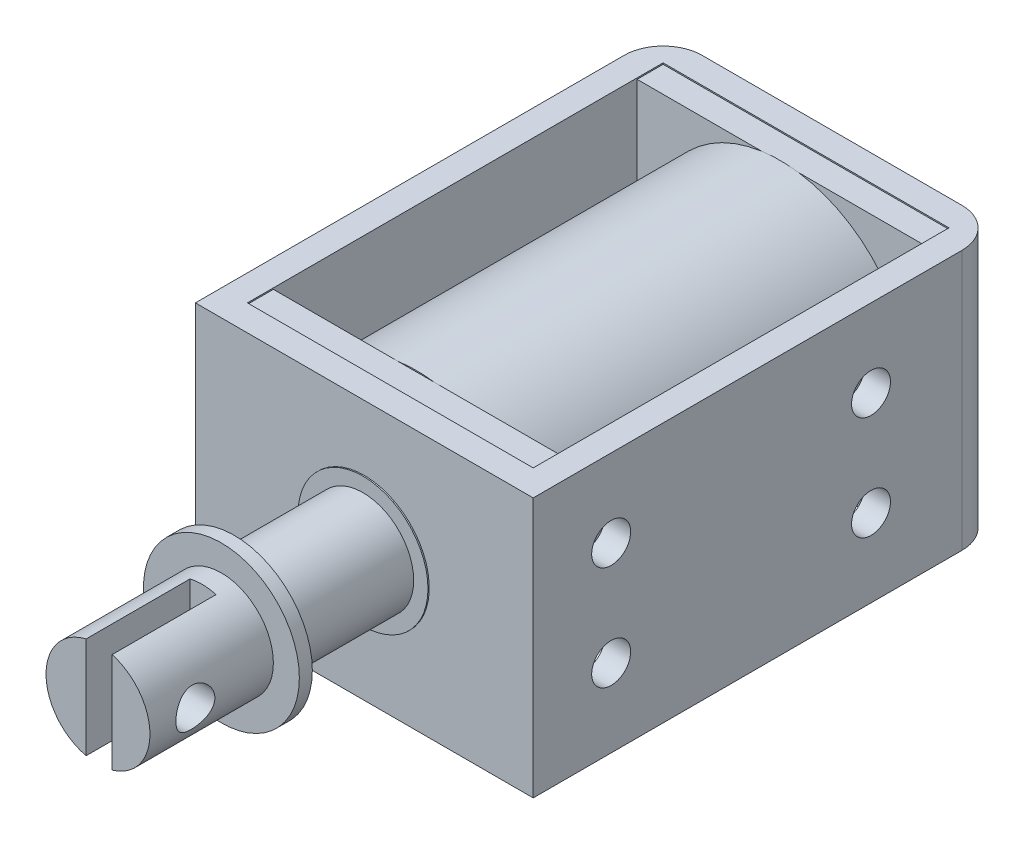
SolidWorks part; units mm, degrees
ref_plane "Front Plane" through (0, 0, 0) normal (0, 0, 1) x (1, 0, 0)
ref_plane "Top Plane" through (0, 0, 0) normal (0, 1, 0) x (1, 0, 0)
ref_plane "Right Plane" through (0, 0, 0) normal (1, 0, 0) x (0, 0, -1)
sketch "Sketch1" plane through (0, 0, 0) normal (0, 1, 0) x (1, 0, 0)
  line L1 (-13, -18) -> (13, -18)
  line L2 (-13, -18) -> (-13, 18)
  line L3 (-13, 18) -> (13, 18)
  line L4 (13, -18) -> (13, 18)
  line L5 (-13, -18) -> (13, 18) construction
  line L6 (-13, 18) -> (13, -18) construction
  point P0 (0, 0)
  dimension "D1" = 26
  dimension "D2" = 36
extrude "Boss-Extrude1" add sketch "Sketch1" along normal blind 20
fillet "Fillet1" radius 3 2 edges at (-13, 10, -18) (13, 10, -18)
sketch "Sketch2" plane through (0, 20, 0) normal (0, 1, 0) x (1, 0, 0)
  line L0 (10, 18) -> (-10, 18) construction
  line L1 (-11, -16) -> (11, -16)
  line L2 (-11, -16) -> (-11, 16)
  line L3 (-11, 16) -> (11, 16)
  line L4 (11, -16) -> (11, 16)
  line L5 (-11, -16) -> (11, 16) construction
  line L6 (-11, 16) -> (11, -16) construction
  line L7 (13, -18) -> (13, 15) construction
  point P0 (0, 0)
  dimension "D1" = 2
  dimension "D2" = 2
extrude "Cut-Extrude1" cut sketch "Sketch2" against normal up to surface (20 mm away) up to face at (0, 0, -5.2071)
sketch "Sketch5" plane through (0, 0, -16) normal (0, 0, 1) x (1, 0, 0)
  line L0 (13, 20) -> (13, 0) construction
  line L1 (-11, -0.1) -> (11, -0.1)
  line L2 (-11, -0.1) -> (-11, 19.9)
  line L3 (-11, 19.9) -> (11, 19.9)
  line L4 (11, -0.1) -> (11, 19.9)
  line L5 (-11, -0.1) -> (11, 19.9) construction
  line L6 (-11, 19.9) -> (11, -0.1) construction
  line L7 (-13, 20) -> (-13, 0) construction
  line L8 (-13, 20) -> (13, 20) construction
  line L9 (-13, 0) -> (13, 0) construction
  point P0 (0, 9.9)
  dimension "D1" = 2
  dimension "D2" = 2
  dimension "D3" = 0.1
  dimension "D4" = 0.1
extrude "Boss-Extrude3" add sketch "Sketch5" along normal blind 2
sketch "Sketch6" plane through (0, 0, 16) normal (0, 0, -1) x (-1, 0, 0)
  line L0 (-10, 20) -> (10, 20) construction
  line L1 (-11, 19.9) -> (11, 19.9)
  line L2 (-11, 19.9) -> (-11, -0.1)
  line L3 (-11, -0.1) -> (11, -0.1)
  line L4 (11, 19.9) -> (11, -0.1)
  line L5 (-11, 19.9) -> (11, -0.1) construction
  line L6 (-11, -0.1) -> (11, 19.9) construction
  line L7 (-13, 0) -> (-13, 20) construction
  point P0 (0, 9.9)
  dimension "D1" = 0.1
  dimension "D2" = 2
extrude "Boss-Extrude4" add sketch "Sketch6" along normal blind 2
sketch "Sketch7" plane through (0, 0, 14) normal (0, 0, -1) x (-1, 0, 0)
  line L0 (13, 20) -> (13, 0) construction
  line L1 (-10, 0) -> (10, 0) construction
  circle A0 centre (0, 10) radius 10
  dimension "D1" = 13
  dimension "D2" = 10
  dimension "D3" = 20
extrude "Boss-Extrude5" add sketch "Sketch7" along normal up to surface (28 mm away) up to face at (0, 6.6, -14)
sketch "Sketch8" plane through (0, 0, -18) normal (0, 0, -1) x (-1, 0, 0)
  line L0 (-10, 20) -> (10, 20) construction
  line L1 (13, 20) -> (13, 0) construction
  circle A0 centre (0, 10) radius 3
  dimension "D1" = 6
  dimension "D2" = 10
  dimension "D3" = 13
extrude "Boss-Extrude6" add sketch "Sketch8" along normal blind 0.5
sketch "Sketch9" plane through (0, 0, -18.5) normal (0, 0, -1) x (-1, 0, 0)
  circle A0 centre (0, 10) radius 3
  dimension "D1" = 6
extrude "Boss-Extrude7" add sketch "Sketch9" along normal blind 2 separate body
fillet "Fillet2" radius 1 2 edges at (-3, 10, -18.5) (-3, 10, -20.5)
sketch "Sketch10" plane through (0, 0, -20.5) normal (0, 0, -1) x (-1, 0, 0)
  line L1 (3.0022, 10) -> (1.5011, 12.6)
  line L2 (1.5011, 12.6) -> (-1.5011, 12.6)
  line L3 (-1.5011, 12.6) -> (-3.0022, 10)
  line L4 (-3.0022, 10) -> (-1.5011, 7.4)
  line L5 (-1.5011, 7.4) -> (1.5011, 7.4)
  line L6 (1.5011, 7.4) -> (3.0022, 10)
  circle A0 centre (0, 10) radius 2.6 construction
  dimension "D1" = 5.2
extrude "Boss-Extrude8" add sketch "Sketch10" along normal blind 2
sketch "Sketch11" plane through (0, 0, -22.5) normal (0, 0, -1) x (-1, 0, 0)
  circle A0 centre (0, 10) radius 2.6
  dimension "D1" = 5.2
extrude "Boss-Extrude9" add sketch "Sketch11" along normal blind 3
fillet "Fillet4" radius 2 1 edges at (-2.6, 10, -25.5)
sketch "Sketch12" plane through (0, 0, 18) normal (0, 0, 1) x (1, 0, 0)
  line L0 (-13, 20) -> (13, 20) construction
  line L1 (13, 20) -> (13, 0) construction
  circle A0 centre (0, 10) radius 3.9
  dimension "D1" = 7.8
  dimension "D2" = 10
  dimension "D3" = 13
extrude "Boss-Extrude10" add sketch "Sketch12" along normal blind 10
sketch "Sketch13" plane through (0, 0, 28) normal (0, 0, 1) x (1, 0, 0)
  circle A0 centre (0, 10) radius 6
  dimension "D1" = 12
extrude "Boss-Extrude11" add sketch "Sketch13" along normal blind 1
sketch "Sketch14" plane through (0, 0, 29) normal (0, 0, 1) x (1, 0, 0)
  circle A0 centre (0, 10) radius 4
  dimension "D1" = 8
extrude "Boss-Extrude12" add sketch "Sketch14" along normal blind 9.5
sketch "Sketch15" plane through (0, 0, 38.5) normal (0, 0, 1) x (1, 0, 0)
  line L1 (-0.9116, 6) -> (1.0884, 6)
  line L2 (-0.9116, 6) -> (-0.9116, 14)
  line L3 (-0.9116, 14) -> (1.0884, 14)
  line L4 (1.0884, 6) -> (1.0884, 14)
  line L5 (-0.9116, 6) -> (1.0884, 14) construction
  line L6 (-0.9116, 14) -> (1.0884, 6) construction
  circle A0 centre (0, 10) radius 4 construction
  circle A1 centre (0, 10) radius 4 construction
  point P0 (0.0884, 10)
  dimension "D1" = 8
  dimension "D2" = 4
  dimension "D3" = 2
  dimension "D4" = 0.9116
extrude "Cut-Extrude3" cut sketch "Sketch15" against normal blind 8
sketch "Sketch16" plane through (-0.9116, 0, 0) normal (1, 0, 0) x (0, 0, -1)
  line L0 (-38.5, 13.8491) -> (-38.5, 6.1509) construction
  line L1 (-38.5, 13.8947) -> (-30.5, 13.8947) construction
  circle A0 centre (-35, 9.8947) radius 1.5
  dimension "D1" = 3
  dimension "D2" = 3.5
  dimension "D3" = 4
extrude "Cut-Extrude4" cut sketch "Sketch16" against normal blind 5 and the other way blind 5
sketch "Sketch17" plane through (0, 0, 18) normal (0, 0, 1) x (1, 0, 0)
  circle A0 centre (0, 10) radius 5
  dimension "D1" = 10
extrude "Boss-Extrude13" add sketch "Sketch17" along normal blind 0.1
sketch "Sketch18" plane through (13, 0, 0) normal (1, 0, 0) x (0, 0, -1)
  line L0 (-18, 0) -> (15, 0) construction
  line L4 (-18, 20) -> (-18, 0) construction
  circle A0 centre (-12, 14) radius 1.5
  circle A1 centre (8, 14) radius 1.5
  circle A2 centre (8, 6) radius 1.5
  circle A3 centre (-12, 6) radius 1.5
  dimension "D1" = 3
  dimension "D2" = 3
  dimension "D3" = 3
  dimension "D4" = 3
  dimension "D5" = 20
  dimension "D6" = 8
  dimension "D7" = 6
  dimension "D9" = 6
extrude "Cut-Extrude5" cut sketch "Sketch18" against normal blind 2
